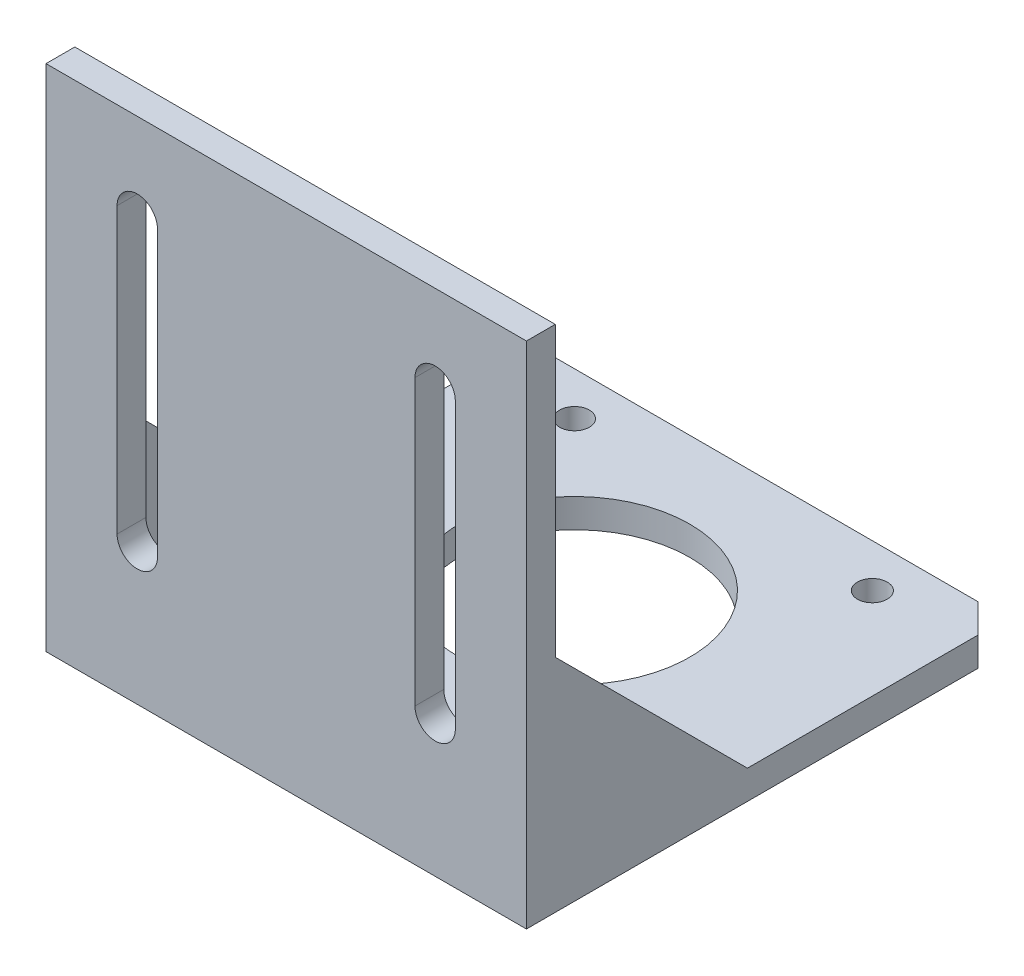
SolidWorks part; units mm, degrees
ref_plane "Front Plane" through (0, 0, 0) normal (0, 0, 1) x (1, 0, 0)
ref_plane "Top Plane" through (0, 0, 0) normal (0, 1, 0) x (1, 0, 0)
ref_plane "Right Plane" through (0, 0, 0) normal (1, 0, 0) x (0, 0, -1)
sketch "BaseSketch1" plane through (0, 0, 0) normal (0, 1, 0) x (1, 0, 0)
  line L0 (0, 0) -> (50, 0)
  line L1 (50, 0) -> (50, 46.9948)
  line L2 (50, 46.9948) -> (46.9948, 50)
  line L3 (46.9948, 50) -> (3.0052, 50)
  line L4 (3.0052, 50) -> (0, 46.9948)
  line L5 (0, 46.9948) -> (0, 0)
  circle A0 centre (25, 30) radius 12
  circle A1 centre (9.5, 45.5) radius 1.55
  circle A2 centre (40.5, 45.5) radius 1.55
  circle A3 centre (40.5, 14.5) radius 1.55
  circle A4 centre (9.5, 14.5) radius 1.55
  dimension "D4" = 3.1
  dimension "D5" = 24
  dimension "D1" = 31
  dimension "D2" = 31
  dimension "D3" = 50
  dimension "D6" = 15.5
  dimension "D7" = 15.5
  dimension "D8" = 9.5
  dimension "D9" = 50
  dimension "D11" = 4.25
  dimension "D10" = 30
extrude "WidthBoss-Extrude1" add sketch "BaseSketch1" along normal blind 3
sketch "Sketch2" plane through (0, 3, 0) normal (0, 1, 0) x (1, 0, 0)
  line L0 (50, 0) -> (50, 46.9948) construction
  line L1 (0, 0) -> (50, 0)
  line L2 (0, 0) -> (0, 3)
  line L3 (0, 3) -> (50, 3)
  line L4 (50, 0) -> (50, 3)
  dimension "D1" = 3
extrude "HeightBoss-Extrude2" add sketch "Sketch2" along normal blind 50
sketch "Sketch3" plane through (0, 0, -3) normal (0, 0, -1) x (-1, 0, 0)
  line L0 (-40.5, 14.3) -> (-40.5, 43.9) construction
  line L1 (-42.6, 14.3) -> (-42.6, 43.9)
  line L2 (-38.4, 14.3) -> (-38.4, 43.9)
  line L3 (-9.5, 14.3) -> (-9.5, 43.9) construction
  line L4 (-11.6, 14.3) -> (-11.6, 43.9)
  line L5 (-7.4, 14.3) -> (-7.4, 43.9)
  line L6 (-50, 53) -> (0, 53) construction
  line L7 (-46.9948, 0) -> (-3.0052, 0) construction
  line L8 (-40.5, 3) -> (-40.5, 0) construction
  line L9 (-9.5, 3) -> (-9.5, 0) construction
  line L10 (-50, 53) -> (-50, 3) construction
  line L12 (0, 53) -> (0, 3) construction
  line L13 (-46.9948, 3) -> (-3.0052, 3) construction
  arc A0 (-42.6, 14.3) -> (-38.4, 14.3) centre (-40.5, 14.3) ccw
  arc A1 (-38.4, 43.9) -> (-42.6, 43.9) centre (-40.5, 43.9) ccw
  arc A2 (-11.6, 14.3) -> (-7.4, 14.3) centre (-9.5, 14.3) ccw
  arc A3 (-7.4, 43.9) -> (-11.6, 43.9) centre (-9.5, 43.9) ccw
  point P2 (-40.5, 29.1)
  point P8 (-9.5, 29.1)
  dimension "D2" = 4.2
  dimension "D1" = 9.1
  dimension "D3" = 29.6
  dimension "D5" = 31
  dimension "D6" = 53
  dimension "D7" = 50
  dimension "D4" = 11.3
extrude "SlotsCut-Extrude1" cut sketch "Sketch3" against normal through all
sketch "WedgeSketch4" plane through (0, 3, 0) normal (0, 1, 0) x (1, 0, 0)
  line L0 (50, 3) -> (0, 3) construction
  line L1 (50, 3) -> (47, 3)
  line L2 (50, 3) -> (50, 23)
  line L3 (50, 23) -> (47, 23)
  line L4 (47, 3) -> (47, 23)
  line L5 (0, 3) -> (3, 3)
  line L6 (0, 3) -> (0, 23)
  line L7 (0, 23) -> (3, 23)
  line L8 (3, 3) -> (3, 23)
  line L9 (50, 3) -> (0, 3) construction
  line L10 (0, 46.9948) -> (0, 3) construction
  line L11 (50, 3) -> (50, 46.9948) construction
  dimension "D1" = 20
  dimension "D2" = 3
extrude "AngleBoss-Extrude3" add sketch "WedgeSketch4" along normal blind 20
chamfer "Chamfer1" distance 20 angle 45 2 edges at (48.5, 23, -23) (1.5, 23, -23)
equation "\"Nema17MountLength\"= 50mm'Spec"
equation "\"D3@BaseSketch1\"=\"Nema17MountLength\""
equation "\"Nema17MountWidth\"= 50mm'Spec"
equation "\"D9@BaseSketch1\"=\"Nema17MountWidth\""
equation "\"Nema17MountSlotHeight\"= 29.6mm'Spec"
equation "\"D1@BaseSketch1\"=\"Nema17MountDistanceBetweenMountHoles\""
equation "\"Nema17MountHeight\"= 53mm'Spec"
equation "\"D1@HeightBoss-Extrude2\"=\"Nema17MountHeight\" - \"Nema17MountThickness\""
equation "\"Nema17MountStepperHoleDistanceFromBack\"= 30mm'Spec"
equation "\"D10@BaseSketch1\"=\"Nema17MountStepperHoleDistanceFromBack\""
equation "\"Nema17MountSlotDiameter\"= 4.2mm'Spec"
equation "\"Nema17MountThickness\"= 3mm'Spec"
equation "\"D2@Sketch3\"=\"Nema17MountSlotDiameter\""
equation "\"Nema17MountDistanceBetweenMountHoles\"= 31mm'Spec"
equation "\"D3@Sketch3\"=\"Nema17MountSlotHeight\""
equation "\"Nema17MountStepperHoleDiameter\"= 24mm'Spec"
equation "\"D5@BaseSketch1\"=\"Nema17MountStepperHoleDiameter\""
